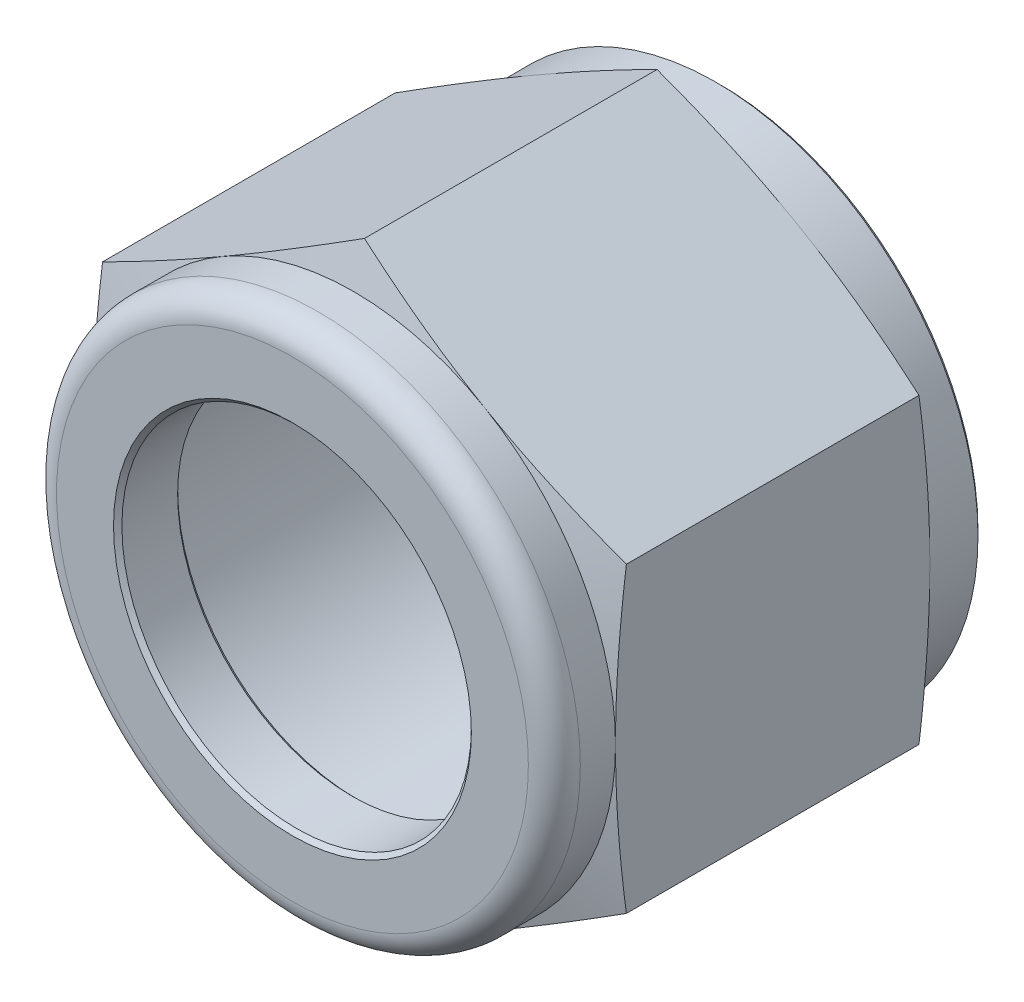
SolidWorks part; units mm, degrees
material "2024 Alloy"
ref_plane "Front Plane" through (0, 0, 0) normal (0, 0, 1) x (1, 0, 0)
ref_plane "Top Plane" through (0, 0, 0) normal (0, 1, 0) x (1, 0, 0)
ref_plane "Right Plane" through (0, 0, 0) normal (1, 0, 0) x (0, 0, -1)
sketch "Sketch0" plane through (0, 0, 0) normal (1, 0, 0) x (0, 0, -1)
  line L0 (0, 0) -> (-25.9334, 0) construction
  line L4 (-25.9334, 15.875) -> (-25.9334, -15.875) construction
  line L5 (-25.9334, 15.875) -> (-25.9334, -15.875) construction
  line L6 (-25.9334, 10.5918) -> (-25.9334, -10.5918) construction
  line L7 (0, 13.4937) -> (0, -13.4937) construction
  line L8 (0, -13.4874) -> (0, 13.4874) construction
  line L9 (0, -13.4874) -> (-2.1167, -13.4874) construction
  point P16 (-22.0472, 0)
  point P20 (-19.1262, 0)
  point P22 (-13.6398, 0)
  point P34 (-3.175, 0)
  point P35 (-22.225, 0)
  dimension "P" = 31.75
  dimension "M" = 25.9334
  dimension "L" = 22.0472
  dimension "S" = 19.1262
  dimension "Q" = 13.6398
  dimension "A" = 21.1836
  dimension "C" = 31.75
  dimension "T" = 26.9875
  dimension "B" = 3.175
  dimension "J" = 19.05
  dimension "H" = 26.9748
  dimension "Pitch" = 2.1167
sketch "Sketch1" plane through (0, 0, 0) normal (0, 0, 1) x (1, 0, 0)
  line L1 (0, 18.3309) -> (-15.875, 9.1654)
  line L2 (-15.875, 9.1654) -> (-15.875, -9.1654)
  line L3 (-15.875, -9.1654) -> (0, -18.3309)
  line L4 (0, -18.3309) -> (15.875, -9.1654)
  line L5 (15.875, -9.1654) -> (15.875, 9.1654)
  line L6 (15.875, 9.1654) -> (0, 18.3309)
  circle A0 centre (0, 0) radius 15.875 construction
extrude "Boss-Extrude1" add sketch "Sketch1" along normal up to vertex (25.9334 mm away) up to point (0, 0, 25.9334)
sketch "Sketch2" plane through (0, 0, 0) normal (1, 0, 0) x (0, 0, -1)
  line L0 (-25.9334, 20.7867) -> (-25.9334, 15.875)
  line L1 (-25.9334, 15.875) -> (-22.225, 15.875)
  line L2 (-22.225, 15.875) -> (-21.567, 18.3309)
  line L3 (-25.9334, 18.3309) -> (0, 18.3309) construction
  line L4 (-21.567, 18.3309) -> (-3.833, 18.3309)
  line L5 (-3.833, 18.3309) -> (-3.175, 15.875)
  line L6 (-3.175, 15.875) -> (-22.225, 15.875) construction
  line L7 (-3.175, 15.875) -> (0, 15.875)
  line L8 (0, 15.875) -> (0, 20.7867)
  line L9 (-25.9334, 20.7867) -> (0, 20.7867)
  line L10 (-3.175, 15.875) -> (-3.175, 0) construction
  line L11 (-22.225, 15.875) -> (-22.225, 0) construction
  line L12 (-25.9334, 10.5918) -> (-25.9334, 0)
  line L13 (-25.9334, 15.875) -> (-25.9334, -15.875) construction
  line L14 (-25.9334, 0) -> (0, 0)
  line L15 (0, 0) -> (0, 12.7204)
  line L16 (-22.0472, 10.5918) -> (-22.0472, 0) construction
  line L17 (-22.0472, 10.5918) -> (-22.0472, 12.4664)
  line L18 (-21.7932, 12.7204) -> (0, 12.7204)
  line L19 (-22.0472, 10.5918) -> (-25.9334, 10.5918)
  line L23 (-19.1262, 0) -> (-19.1262, 12.7204) construction
  arc A0 (-22.0472, 12.4664) -> (-21.7932, 12.7204) centre (-21.7932, 12.4664) cw
  dimension "D3" = 0.254
  dimension "D1" = 15
  dimension "D2" = 15
  dimension "D4" = 0.7733
revolve "Cut-Revolve1" cut sketch "Sketch2" angle 360 about L0
sketch "Sketch3" [suppressed] plane through (0, 0, 0) normal (0, 0, -1) x (-1, 0, 0)
  circle A0 centre (0, 0) radius 12.7204
  circle A1 centre (0, 0) radius 12.7204 construction
  point P3 (0, 12.7204)
fillet "Fillet1" radius 1.5748 1 edges at (15.875, 0, 25.9334)
chamfer "Chamfer1" distance 0.254 angle 45 1 edges at (15.875, 0, 0)
chamfer "Chamfer2" distance 0.254 angle 45 2 edges at (0, 10.5918, 22.0472) (0, 10.5918, 25.9334)
ref_axis "Centre Axis 1" through (0, 0, 25.2505) along (0, 0, -1)
curve "Helix/Spiral1" [suppressed] pitch 2.1167 height 21.2429 turns 10.036 parameters "Pitch"=2.1167
sketch "Sketch4" [suppressed] plane through (0, 0, 0) normal (1, 0, 0) x (0, 0, -1)
  line L0 (-0.248, 12.2908) -> (1.8686, 12.2908) construction
  line L1 (1.8686, 12.2908) -> (0.8103, 14.1239) construction
  line L2 (0.8103, 14.1239) -> (-0.248, 12.2908) construction
  line L3 (0.7111, 13.952) -> (0.9095, 13.952) construction
  line L4 (0.8103, 12.7204) -> (0.8103, 12.2908) construction
  line L5 (0, 12.7204) -> (1.6206, 12.7204) construction
  line L6 (0.8103, 14.1239) -> (0.8103, 13.952) construction
  line L7 (0.7111, 13.952) -> (-0.124, 12.5056)
  line L8 (-0.124, 12.5056) -> (1.7446, 12.5056)
  line L9 (1.7446, 12.5056) -> (0.9095, 13.952)
  arc A0 (0.9095, 13.952) -> (0.7111, 13.952) centre (0.8103, 13.8947) ccw
  point P6 (0.8103, 12.5056)
  dimension "D1" = 2.1167
  dimension "D2" = 1.8331
  dimension "D4" = 0.4296
  dimension "D3" = 0.1719
  dimension "D5" = 1.2316
sweep "Cut-Sweep1" [suppressed] cut profiles "Sketch4" path "Helix/Spiral1"
sketch "Sketch5" [suppressed] plane through (0, 0, 0) normal (0, 0, -1) x (-1, 0, 0)
  circle A0 centre (0, 0) radius 13.4874
extrude "Cut-Extrude1" [suppressed] cut sketch "Sketch5" against normal through all draft 45
sketch "Sketch6" [suppressed] plane through (0, 0, 0) normal (1, 0, 0) x (0, 0, -1)
  line L0 (-22.0472, 14.1239) -> (-13.6398, 14.1239)
  line L1 (-13.6398, 14.1239) -> (-19.1262, 12.7204)
  line L2 (-19.1262, 12.7204) -> (-22.0472, 12.7204)
  line L3 (-22.0472, 12.7204) -> (-22.0472, 14.1239)
  line L4 (-13.6398, 0) -> (-13.6398, 14.1239) construction
  line L5 (-19.1262, 0) -> (-19.1262, 12.7204) construction
  line L7 (-22.0472, 12.7204) -> (-22.0472, 0) construction
  line L8 (-21.7932, 12.7204) -> (0, 12.7204) construction
  line L9 (-13.6398, 14.1239) -> (0.8103, 14.1239) construction
revolve "Revolve1" [suppressed] add sketch "Sketch6" angle 360 about L0
sketch "SketchX" [suppressed] plane through (0, 0, 0) normal (0, 0, -1) x (-1, 0, 0)
  line L0 (0, 0) -> (-6.7437, 11.6804) construction
  line L1 (-7.9375, 13.7482) -> (-15.875, 9.1654) construction
  circle A0 centre (0, 0) radius 13.4874 construction
equation "\"D3@Helix/Spiral1\"= \"Pitch@Sketch0\" + \"S@Sketch0\""
equation "\"D1@Sketch4\"=\"Pitch@Sketch0\""
equation "\"Pitch@Helix/Spiral1\"=\"Pitch@Sketch0\""
